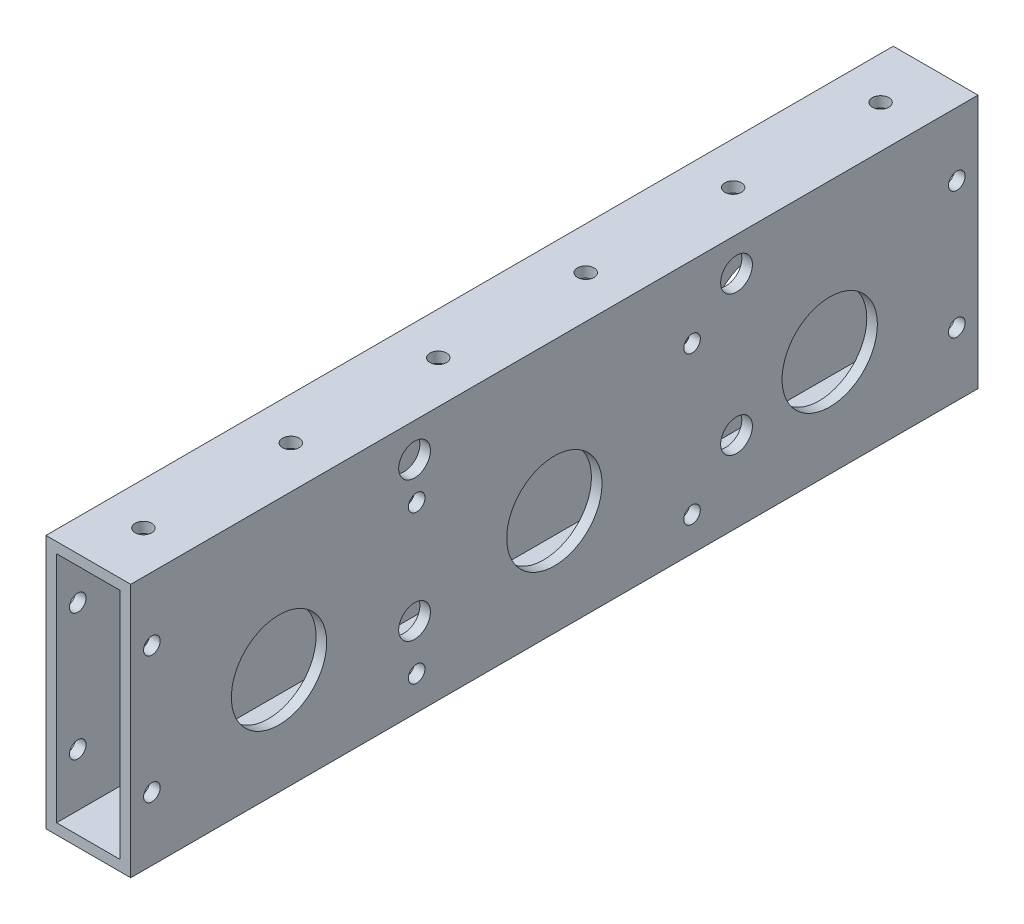
SolidWorks part; units mm, degrees
material "6061-T6 (SS)"
ref_plane "Front Plane" through (0, 0, 0) normal (0, 0, 1) x (1, 0, 0)
ref_plane "Top Plane" through (0, 0, 0) normal (0, 1, 0) x (1, 0, 0)
ref_plane "Right Plane" through (0, 0, 0) normal (1, 0, 0) x (0, 0, -1)
sketch "Sketch1" plane through (0, 0, 0) normal (1, 0, 0) x (0, 0, -1)
  line L1 (-127, 38.1) -> (127, 38.1)
  line L2 (-127, 38.1) -> (-127, -38.1)
  line L3 (-127, -38.1) -> (127, -38.1)
  line L4 (127, 38.1) -> (127, -38.1)
  line L5 (-127, 38.1) -> (127, -38.1) construction
  line L6 (-127, -38.1) -> (127, 38.1) construction
  point P0 (0, 0)
  dimension "D1" = 76.2
  dimension "D2" = 254
extrude "Boss-Extrude1" add sketch "Sketch1" along normal blind 25.4
shell "Shell1" thickness 3.175 removed face at (12.7, 0, -127) removed face at (12.7, 0, 127)
sketch "Sketch2" plane through (25.4, 0, 0) normal (1, 0, 0) x (0, 0, -1)
  line L0 (-127, -38.1) -> (127, -38.1) construction
  line L1 (-82.55, -6.35) -> (0, -6.35) construction
  line L2 (-41.275, -27.94) -> (-41.275, -6.35) construction
  line L3 (0, -6.35) -> (82.55, -6.35) construction
  line L4 (41.275, -27.94) -> (41.275, -6.35) construction
  line L5 (127, 38.1) -> (-127, 38.1) construction
  line L6 (54.61, 27.94) -> (-41.91, 27.94) construction
  line L7 (54.61, 27.94) -> (54.61, -13.97) construction
  line L8 (54.61, -13.97) -> (-41.91, -13.97) construction
  line L9 (-41.91, 27.94) -> (-41.91, -13.97) construction
  line L10 (-127, -38.1) -> (127, -38.1) construction
  circle A0 centre (0, -6.35) radius 14.2875
  circle A1 centre (-82.55, -6.35) radius 14.2875
  circle A2 centre (82.55, -6.35) radius 14.2875
  circle A3 centre (-82.55, -6.35) radius 38.1 construction
  circle A4 centre (0, -6.35) radius 38.1 construction
  circle A5 centre (82.55, -6.35) radius 38.1 construction
  circle A6 centre (-41.275, -27.94) radius 6.35 construction
  circle A7 centre (41.275, -27.94) radius 6.35 construction
  circle A8 centre (-41.275, 16.51) radius 6.35 construction
  circle A9 centre (41.275, 16.51) radius 6.35 construction
  point P11 (0, 0)
  dimension "D1" = 28.575
  dimension "D5" = 76.2
  dimension "D7" = 12.7
  dimension "D2" = 31.75
  dimension "D3" = 82.55
  dimension "D4" = 82.55
  dimension "D6" = 0
  dimension "D8" = 10.16
  dimension "D9" = 44.45
  dimension "D10" = 41.91
  dimension "D11" = 96.52
  dimension "D12" = 10.16
  dimension "D13" = 24.13
extrude "Cut-Extrude1" cut sketch "Sketch2" against normal through all
sketch "Sketch3" plane through (25.4, 0, 0) normal (1, 0, 0) x (0, 0, -1)
  line L0 (-120.65, 19.05) -> (-120.65, -19.05) construction
  line L1 (-127, 38.1) -> (-127, -38.1) construction
  point P2 (-120.65, 0)
  point P3 (-127, 0)
  dimension "D1" = 38.1
  dimension "D2" = 6.35
hole_wizard "#10 Clearance Hole1" positions "Sketch4" profile "Sketch6" hole size "#10" standard "ANSI Inch" end condition through all
sketch "Sketch4" plane through (25.4, 0, 0) normal (1, 0, 0) x (0, 0, -1)
  point P0 (-120.65, 19.05)
  point P3 (-120.65, -19.05)
sketch "Sketch6" plane through (25.4, 19.05, 120.65) normal (0, 1, 0) x (0, 0, -1)
  line L0 (0, 0) -> (0, 25.4)
  line L1 (0, 25.4) -> (2.4892, 25.4)
  line L2 (2.4892, 25.4) -> (2.4892, 0)
  line L5 (2.4892, 0) -> (0, 0)
  line L11 (0, -6.35) -> (0, 107.95) construction
  dimension "Thru Hole Dia." = 4.9784
  dimension "Thru Hole Depth" = 25.4
mirror "Mirror1" about plane through (0, 0, 0) normal (0, 0, 1) of "#10 Clearance Hole1"
hole_wizard "#10 Clearance Hole2" positions "Sketch7" profile "Sketch8" hole size "#10" standard "ANSI Inch" end condition through all
sketch "Sketch7" plane through (25.4, 0, 0) normal (1, 0, 0) x (0, 0, -1)
  point P0 (-41.275, -27.94)
  point P3 (41.275, -27.94)
  point P7 (-41.275, 16.51)
  point P10 (41.275, 16.51)
sketch "Sketch8" plane through (25.4, -27.94, 41.275) normal (0, 1, 0) x (0, 0, -1)
  line L0 (0, 0) -> (0, 25.4)
  line L1 (0, 25.4) -> (2.4892, 25.4)
  line L2 (2.4892, 25.4) -> (2.4892, 0)
  line L5 (2.4892, 0) -> (0, 0)
  line L11 (0, -6.35) -> (0, 107.95) construction
  dimension "Thru Hole Dia." = 4.9784
  dimension "Thru Hole Depth" = 25.4
hole_wizard "3/8 (0.375) Diameter Hole1" positions "Sketch9" profile "Sketch10" hole size "3/8" standard "ANSI Inch"
sketch "Sketch9" plane through (0, 0, 0) normal (-1, 0, 0) x (0, 0, 1)
  point P0 (-41.275, -27.94)
  point P3 (41.275, -27.94)
  point P7 (41.275, 16.51)
  point P10 (-41.275, 16.51)
sketch "Sketch10" plane through (0, -27.94, -41.275) normal (0, 1, 0) x (0, 0, 1)
  line L0 (0, 0) -> (0, 15.5616)
  line L1 (0, 15.5616) -> (4.7625, 12.7)
  line L2 (4.7625, 12.7) -> (4.7625, 0)
  line L5 (4.7625, 0) -> (0, 0)
  line L10 (0, 15.5616) -> (-4.7625, 12.7) construction
  line L11 (0, -6.35) -> (0, 107.95) construction
  dimension "Hole Dia." = 9.525
  dimension "Hole Depth" = 12.7
  dimension "Drill Angle" = 118
hole_wizard "3/8 (0.375) Diameter Hole2" positions "Sketch11" profile "Sketch12" hole size "3/8" standard "ANSI Inch"
sketch "Sketch11" plane through (25.4, 0, 0) normal (1, 0, 0) x (0, 0, -1)
  point P0 (-41.91, 27.94)
  point P3 (54.61, 27.94)
  point P6 (54.61, -13.97)
  point P9 (-41.91, -13.97)
sketch "Sketch12" plane through (25.4, 27.94, 41.91) normal (0, 1, 0) x (0, 0, -1)
  line L0 (0, 0) -> (0, 15.5616)
  line L1 (0, 15.5616) -> (4.7625, 12.7)
  line L2 (4.7625, 12.7) -> (4.7625, 0)
  line L5 (4.7625, 0) -> (0, 0)
  line L10 (0, 15.5616) -> (-4.7625, 12.7) construction
  line L11 (0, -6.35) -> (0, 107.95) construction
  dimension "Hole Dia." = 9.525
  dimension "Hole Depth" = 12.7
  dimension "Drill Angle" = 118
hole_wizard "#10 Clearance Hole3" positions "Sketch13" profile "Sketch14" hole size "#10" standard "ANSI Inch"
sketch "Sketch13" plane through (0, 0, 0) normal (-1, 0, 0) x (0, 0, 1)
  point P0 (41.91, 27.94)
  point P3 (-54.61, 27.94)
  point P6 (-54.61, -13.97)
  point P9 (41.91, -13.97)
sketch "Sketch14" plane through (0, 27.94, 41.91) normal (0, 1, 0) x (0, 0, 1)
  line L0 (0, 0) -> (0, 14.1957)
  line L1 (0, 14.1957) -> (2.4892, 12.7)
  line L2 (2.4892, 12.7) -> (2.4892, 0)
  line L5 (2.4892, 0) -> (0, 0)
  line L10 (0, 14.1957) -> (-2.4892, 12.7) construction
  line L11 (0, -6.35) -> (0, 107.95) construction
  dimension "Hole Dia." = 4.9784
  dimension "Hole Depth" = 12.7
  dimension "Drill Angle" = 118
sketch "Sketch15" plane through (0, -38.1, 0) normal (0, -1, 0) x (1, 0, 0)
  line L0 (12.7, 110.49) -> (12.7, -110.49) construction
  line L1 (25.4, 127) -> (25.4, -127) construction
  line L2 (25.4, 127) -> (0, 127) construction
  point P2 (25.4, 0)
  point P3 (12.7, 0)
  point P7 (12.7, 127)
  dimension "D1" = 16.51
hole_wizard "#10 Clearance Hole4" positions "Sketch16" profile "Sketch17" hole size "#10" standard "ANSI Inch" end condition through all
sketch "Sketch16" plane through (0, -38.1, 0) normal (0, -1, 0) x (-1, 0, 0)
  point P0 (-12.7, -110.49)
  point P3 (-12.7, 110.49)
sketch "Sketch17" plane through (12.7, -38.1, 110.49) normal (1, 0, 0) x (0, 0, -1)
  line L0 (0, 0) -> (0, 76.2)
  line L1 (0, 76.2) -> (2.4892, 76.2)
  line L2 (2.4892, 76.2) -> (2.4892, 0)
  line L5 (2.4892, 0) -> (0, 0)
  line L11 (0, -6.35) -> (0, 107.95) construction
  dimension "Thru Hole Dia." = 4.9784
  dimension "Thru Hole Depth" = 76.2
sketch "Sketch18" plane through (0, 38.1, 0) normal (0, 1, 0) x (1, 0, 0)
  line L0 (25.4, 127) -> (0, 127) construction
  line L1 (25.4, 127) -> (25.4, -127) construction
  point P0 (12.7, 127)
  point P1 (12.7, 66.294)
  point P4 (25.4, 0)
  point P6 (12.7, 22.098)
  dimension "D1" = 44.196
  dimension "D2" = 22.098
hole_wizard "#10 Clearance Hole5" positions "Sketch19" profile "Sketch21" hole size "#10" standard "ANSI Inch" end condition through all
sketch "Sketch19" plane through (0, 38.1, 0) normal (0, 1, 0) x (1, 0, 0)
  point P0 (12.7, 66.294)
  point P4 (12.7, 22.098)
sketch "Sketch21" plane through (12.7, 38.1, -66.294) normal (1, 0, 0) x (0, 0, 1)
  line L0 (0, 0) -> (0, 76.2)
  line L1 (0, 76.2) -> (2.4892, 76.2)
  line L2 (2.4892, 76.2) -> (2.4892, 0)
  line L5 (2.4892, 0) -> (0, 0)
  line L11 (0, -6.35) -> (0, 107.95) construction
  dimension "Thru Hole Dia." = 4.9784
  dimension "Thru Hole Depth" = 76.2
mirror "Mirror2" about plane through (0, 0, 0) normal (0, 0, 1) of "#10 Clearance Hole5"
